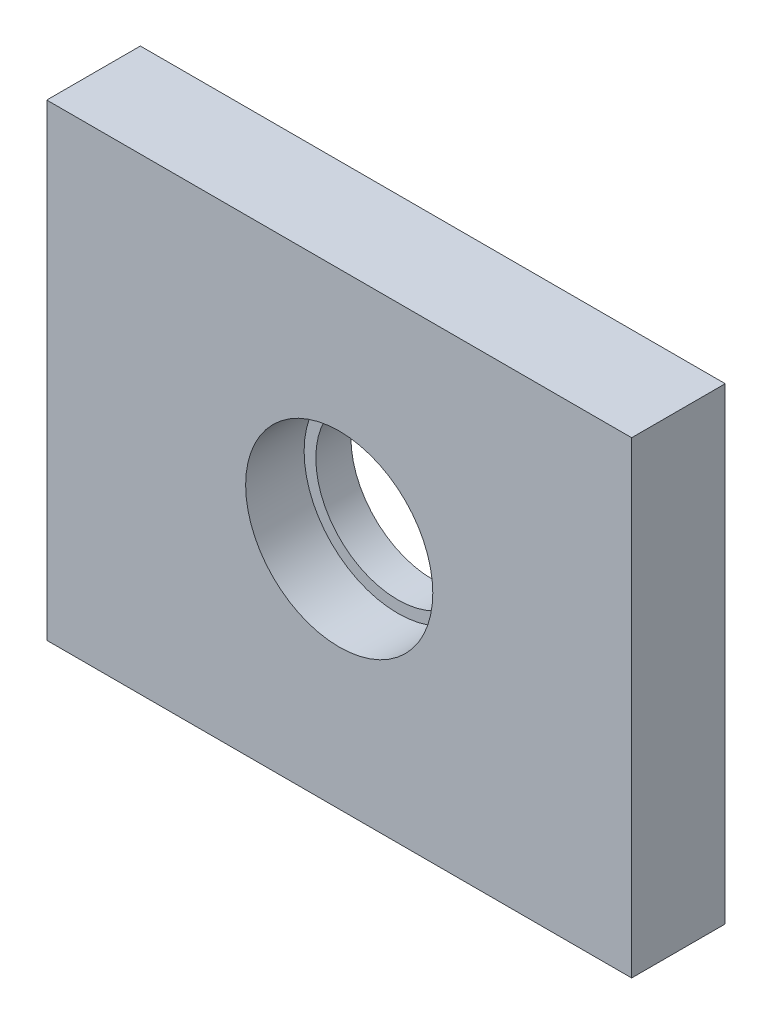
SolidWorks part; units mm, degrees
ref_plane "Front" through (0, 0, 0) normal (0, 0, 1) x (1, 0, 0)
ref_plane "Top" through (0, 0, 0) normal (0, 1, 0) x (1, 0, 0)
ref_plane "Right" through (0, 0, 0) normal (1, 0, 0) x (0, 0, -1)
sketch "Esquisse1" plane through (0, 0, 0) normal (0, 0, 1) x (1, 0, 0)
  line L0 (25, 0) -> (25, 20) construction
  line L1 (0, 0) -> (50, 0)
  line L2 (0, 0) -> (0, 40)
  line L3 (0, 40) -> (50, 40)
  line L4 (50, 0) -> (50, 40)
  circle A0 centre (25, 20) radius 7
  dimension "D1" = 20
  dimension "D2" = 14
  dimension "D3" = 50
  dimension "D4" = 40
extrude "Boss.-Extru.1" add sketch "Esquisse1" along normal blind 8
sketch "Esquisse2" plane through (0, 0, 8) normal (0, 0, 1) x (1, 0, 0)
  circle A0 centre (25, 20) radius 8
  dimension "D1" = 16
extrude "Enlèv. mat.-Extru.1" cut sketch "Esquisse2" against normal blind 5
